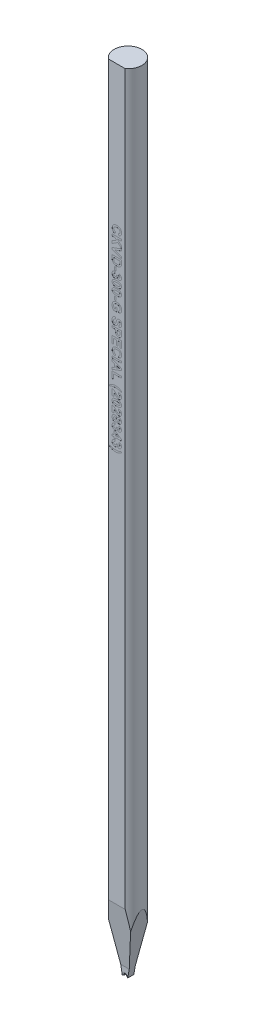
SolidWorks part; units mm, degrees
ref_plane "Ebene vorne" through (0, 0, 0) normal (0, 0, 1) x (1, 0, 0)
ref_plane "Ebene oben" through (0, 0, 0) normal (0, 1, 0) x (1, 0, 0)
ref_plane "Ebene rechts" through (0, 0, 0) normal (1, 0, 0) x (0, 0, -1)
sketch "sketch_TL_cutting" plane through (0, 0, 0) normal (0, 1, 0) x (1, 0, 0)
  circle A0 centre (0, 0) radius 1.4986
extrude "TL_cutting" add sketch "sketch_TL_cutting" along normal blind 85.4964
sketch "sketch_TDF_grinding" plane through (0, 0, 0) normal (0, 1, 0) x (1, 0, 0)
  line L0 (0, 0) -> (0, -1.2014) construction
  line L1 (-1.5086, -4.2186) -> (1.5086, -4.2186)
  line L2 (-1.5086, -4.2186) -> (-1.5086, -1.2014)
  line L3 (-1.5086, -1.2014) -> (1.5086, -1.2014)
  line L4 (1.5086, -4.2186) -> (1.5086, -1.2014)
  circle A1 centre (0, 0) radius 1.4986 construction
  point P9 (0, -4.2186)
  dimension "TD_2Offset_X" = 3.0172
  dimension "TD_2Offset_Z" = 3.0172
extrude "TDF_grinding" cut sketch "sketch_TDF_grinding" along normal through all
sketch "sketch_engraving" plane through (0, 0, 1.2014) normal (0, 0, 1) x (1, 0, 0)
  line L0 (0.8958, 85.4964) -> (-0.8958, 85.4964) construction
  line L6 (-0.8958, 0) -> (0.8958, 0) construction
  line L7 (0, 0) -> (0, 70.4964) construction
  line L8 (-0.5, 70.4964) -> (-0.5, 0) construction
  text T0 "CKVD-300-G SPECIAL (2028343)" font "Arial" height 1
  dimension "D2" = 0.5
  dimension "EngravingStart" = 15
extrude "engraving" cut sketch "sketch_engraving" against normal blind 0.005
sketch "sketch_VW_VR_grinding" plane through (0, 0, 0) normal (0, 0, 1) x (1, 0, 0)
  line L0 (-1.4936, -0.01) -> (-1.4936, 0.8842)
  line L1 (1.4936, -0.01) -> (1.4936, 0.8842)
  line L2 (-1.4936, 0) -> (1.4936, 0) construction
  line L3 (-1.5086, 0.8892) -> (-1.4986, 0.8892)
  line L4 (1.4986, 0.8892) -> (1.5086, 0.8892)
  line L5 (-1.5086, 0.8892) -> (-1.5086, -0.01)
  line L6 (-1.5086, -0.01) -> (-1.4936, -0.01)
  line L7 (1.4936, -0.01) -> (1.5086, -0.01)
  line L8 (1.5086, -0.01) -> (1.5086, 0.8892)
  line L9 (-1.4986, 0.8892) -> (-1.4986, 0.8842) construction
  line L10 (-1.4936, 0.8842) -> (-1.4986, 0.8842) construction
  line L11 (1.4936, 0.8842) -> (1.4986, 0.8842) construction
  line L12 (1.4986, 0.8892) -> (1.4986, 0.8842) construction
  arc A0 (-1.4986, 0.8892) -> (-1.4936, 0.8842) centre (-1.4986, 0.8842) cw
  arc A2 (1.4936, 0.8842) -> (1.4986, 0.8892) centre (1.4986, 0.8842) cw
  dimension "D2" = 0.005
  dimension "D1" = 0.01
  dimension "D4" = 3.0172
extrude "VW_VR_grinding" cut sketch "sketch_VW_VR_grinding" against normal blind 1.5086 and the other way blind 1.5086
sketch "sketch_ISA_grinding" plane through (0, 0, 0) normal (0, 0, 1) x (1, 0, 0)
  line L0 (-0.2997, 0) -> (-1.5086, 6.8559)
  line L4 (1.5086, 6.8559) -> (0.2997, 0)
  line L5 (0.2997, 0) -> (-0.2997, 0)
  line L6 (0, 0) -> (0, 30.49) construction
  line L7 (-1.5086, 6.8559) -> (-1.5086, -0.01)
  line L12 (-1.5086, -0.01) -> (1.5086, -0.01)
  line L13 (1.5086, -0.01) -> (1.5086, 6.8559)
  dimension "ISA" = 20
  dimension "TD_2Offset" = 3.0172
  dimension "Offset" = 0.01
extrude "ISA_grinding" cut sketch "sketch_ISA_grinding" against normal blind 1.5086 and the other way blind 1.5086
sketch "sketch_pre_FRX_BRX" plane through (0, 0, 0) normal (1, 0, 0) x (0, 0, -1)
  line L0 (1.4986, -0.01) -> (1.4986, 3.9152) construction
  line L1 (-1.2014, -0.01) -> (-1.2014, 0.8892) construction
  line L2 (-0.3251, -0.01) -> (-0.3251, 0.8892)
  line L3 (-0.3251, 0.8892) -> (-1.5086, 0.8892)
  line L4 (-1.5086, 0.8892) -> (-1.5086, -0.01)
  line L5 (-1.5086, -0.01) -> (-0.3251, -0.01)
  line L6 (0.3251, -0.01) -> (0.3251, 0.8892)
  line L7 (0.3251, 0.8892) -> (1.5086, 0.8892)
  line L8 (1.5086, 0.8892) -> (1.5086, -0.01)
  line L9 (1.5086, -0.01) -> (0.3251, -0.01)
  dimension "D3" = 0.01
  dimension "D4" = 0.8992
  dimension "D5" = 3.0172
  dimension "D6" = 0.6502
  dimension "D2" = 0.01
  dimension "D7" = 1.8237
extrude "pre_FRX_BRX" cut sketch "sketch_pre_FRX_BRX" against normal blind 1.5086 and the other way blind 1.5086
sketch "sketch_contour_V-Groove" plane through (0, 0, 0) normal (1, 0, 0) x (0, 0, -1)
  line L0 (-1.2014, 0.1905) -> (0, 0.1905)
  line L1 (0, 0.1905) -> (1.4986, 0.1905)
  line L2 (1.4986, -0.8411) -> (1.4986, 1.3178) construction
  line L3 (-1.2014, -0.9209) -> (-1.2014, 1.9363) construction
  line L4 (-1.2014, 0) -> (1.4986, 0) construction
  line L5 (0.3251, 0) -> (0.3251, 0.1905) construction
  line L6 (-0.3251, 0) -> (-0.3251, 0.1905) construction
  dimension "D1" = 0
ref_plane "front" through (0, 0, 1.2014) normal (0, 0, 1) x (1, 0, 0)
ref_plane "back" through (0, 0, -1.4986) normal (0, 0, 1) x (1, 0, 0)
sketch "sketch_section_V-Groove" plane through (0, 0, 1.2014) normal (0, 0, 1) x (1, 0, 0)
  line L0 (-1.499, -1.905) -> (-0.0499, 0.1645)
  line L2 (0.0499, 0.1645) -> (1.499, -1.905)
  line L3 (-1.499, -1.905) -> (1.499, -1.905)
  line L4 (0, -1.905) -> (0, 0.1905) construction
  line L5 (-0.1651, 0) -> (0.1651, 0) construction
  arc A0 (0.0499, 0.1645) -> (-0.0499, 0.1645) centre (0, 0.1296) ccw
  dimension "GA" = 70
sweep "V-Groove_EDM" cut profiles "sketch_section_V-Groove" path "sketch_contour_V-Groove"
fillet "FR_EDM" radius 0.1499 3 edges at (0.1075, 0.0823, 0.3251) (0, 0.1905, 0.3251) (-0.1075, 0.0823, 0.3251)
fillet "BR_EDM" radius 0.1499 3 edges at (0.1075, 0.0823, -0.3251) (0, 0.1905, -0.3251) (-0.1075, 0.0823, -0.3251)
sketch "sketch_FA_BA_grinding" plane through (0, 0, 0) normal (1, 0, 0) x (0, 0, -1)
  line L2 (2.4986, 16.3643) -> (2.4986, -0.1)
  line L3 (2.4986, -0.1) -> (0.3251, -0.1)
  line L5 (0.3251, -0.1) -> (0.3251, 0.8992)
  line L6 (0.3251, 0.8992) -> (2.4986, 16.3643)
  line L7 (1.4986, -0.1) -> (1.4986, 9.2489) construction
  line L8 (-1.2014, 7.1344) -> (-1.2014, -0.1) construction
  line L9 (-3.2728, 21.8732) -> (-0.3251, 0.8992)
  line L10 (-0.3251, 0.8992) -> (-0.3251, -0.1)
  line L11 (-0.3251, -0.1) -> (-3.2728, -0.1)
  line L12 (-3.2728, -0.1) -> (-3.2728, 21.8732)
  line L13 (-0.3251, 0.8992) -> (0.3251, 0.8992) construction
  dimension "D4" = 1
  dimension "D1" = 0.1
  dimension "FA" = 8
  dimension "BA" = 8
extrude "FA_BA_grinding" cut sketch "sketch_FA_BA_grinding" against normal blind 1.5086 and the other way blind 1.5086
sketch "sketch_groove_dimensions" plane through (0, 0, 0) normal (1, 0, 0) x (0, 0, -1)
  line L0 (-0.1753, 0.1905) -> (0.1753, 0.1905)
  line L1 (-0.3251, 0) -> (-0.3251, 0.3404) construction
  line L2 (1.4986, 0) -> (1.4986, 0.4166) construction
  line L3 (0.3251, 0) -> (0.3251, 0.3404) construction
  line L4 (-1.2014, 0) -> (-1.2014, 0.3999) construction
  arc A0 (0.1753, 0.1905) -> (0.3251, 0.3404) centre (0.1753, 0.3404) ccw
  arc A1 (-0.1753, 0.1905) -> (-0.3251, 0.3404) centre (-0.1753, 0.3404) cw
equation "\"_Offset\"=0.01mm"
equation "\"TL\"=85.4964mm"
equation "\"TD\"=2.9972mm"
equation "\"TDF\"=2.70002mm"
equation "\"BA\"=8deg"
equation "\"ISA\"=20deg"
equation "\"FA\"=8deg"
equation "\"GR\"=0.06096mm"
equation "\"GA\"=70deg"
equation "\"GD\"=0.1905mm"
equation "\"FL\"=0.65024mm"
equation "\"F\"=0.35052mm"
equation "\"FX\"=0.8763mm"
equation "\"B\"=0.3302mm"
equation "\"VW\"=0mm"
equation "\"cleaned_VR\"= IIF ( \"VR\" > 0 , \"VR\" , \"E\" - \"_Offset\" )"
equation "\"cleaned_VW\"= IIF ( \"VW\" > 0 , \"VW\" , \"TD\" - \"_Offset\" )"
equation "\"back_edge\"= \"TD\" / 2 - \"X\""
equation "\"side_edge_Offset\"= \"TD\" / 2 + \"_Offset\""
equation "\"TD@sketch_TL_cutting\"=\"TD\""
equation "\"TL@TL_cutting\"=\"TL\""
equation "\"TDF@sketch_TDF_grinding\"=\"TDF\""
equation "\"TD_2Offset_X@sketch_TDF_grinding\"=\"TD\"+2*\"_Offset\""
equation "\"TD_2Offset_Z@sketch_TDF_grinding\"=\"TD\"+2*\"_Offset\""
equation "\"TL_Offset\"= \"TL\" + \"_Offset\""
equation "\"ISA@sketch_ISA_grinding\"=\"ISA\""
equation "\"W@sketch_ISA_grinding\"=\"W\""
equation "\"TD_2Offset@sketch_ISA_grinding\"=\"TD\"+2*\"_Offset\""
equation "\"Offset@sketch_ISA_grinding\"=\"_Offset\""
equation "\"05TD_Offset_posZ@ISA_grinding\"=\"side_edge_Offset\""
equation "\"05TD_Offset_negZ@ISA_grinding\"=\"side_edge_Offset\""
equation "\"E\"=0.89916mm"
equation "\"cleaned_X\"= IIF ( \"X\" > 0 , \"X\" , \"TD\" / 2 - \"FL\" / 2 )"
equation "\"FR\"=0.14986mm"
equation "\"BR\"=0.14986mm"
equation "\"D1\"= \"side_edge_Offset\""
equation "\"D2\"= \"side_edge_Offset\""
equation "\"TDF@sketch_FA_BA_grinding\" = \"TDF\""
equation "\"FL@sketch_FA_BA_grinding\"=\"FL\""
equation "\"E@sketch_FA_BA_grinding\" = \"E\""
equation "\"D1@FA_BA_grinding\"=\"side_edge_Offset\""
equation "\"D2@FA_BA_grinding\"=\"side_angle_Offset\""
equation "\"10GD@sketch_section_V-Groove\" = 10 * \"GD\""
equation "\"GA@sketch_section_V-Groove\" = \"GA\""
equation "\"GD@sketch_section_V-Groove\" = \"GD\""
equation "\"B@sketch_section_V-Groove\" = \"B\""
equation "\"GD@sketch_contour_V-Groove\" = \"GD\""
equation "\"cleaned_FRX\"= IIF ( \"FRX\" > 0 , \"FRX\" , \"FR\" )"
equation "\"cleaned_BRX\"= IIF ( \"BRX\" > 0 , \"BRX\" , \"BR\" )"
equation "\"FL_groove_angle\"=0deg"
equation "\"D3@sketch_pre_FRX_BRX\" = \"_Offset\""
equation "\"D4@sketch_pre_FRX_BRX\" = \"E\""
equation "\"D5@sketch_pre_FRX_BRX\" = 2 * \"side_edge_Offset\""
equation "\"D6@sketch_pre_FRX_BRX\" = \"FL\" + ( \"FR\" - \"cleaned_FRX\" ) + ( \"BR\" - \"cleaned_BRX\" )"
equation "\"TD/2@sketch_pre_FRX_BRX\" = \"TD\" / 2"
equation "\"TDF@sketch_pre_FRX_BRX\" = \"TDF\""
equation "\"D2@sketch_pre_FRX_BRX\" = \"_Offset\""
equation "\"D1@pre_FRX_BRX\" = \"side_edge_Offset\""
equation "\"D2@pre_FRX_BRX\" = \"side_edge_Offset\""
equation "\"D1@BR_EDM\"=\"BR\""
equation "\"TD/2@sketch_FA_BA_grinding\" = \"TD\" / 2"
equation "\"TD/2@sketch_contour_V-Groove\" = \"TD\" / 2"
equation "\"TDF@sketch_contour_V-Groove\" = \"TDF\""
equation "\"D1@sketch_contour_V-Groove\"=\"FL_groove_angle\""
equation "\"FL@sketch_contour_V-Groove\"=\"FL\""
equation "\"FL/2@sketch_contour_V-Groove\" = \"FL\" / 2"
equation "\"D1@FR_EDM\"=\"FR\""
equation "\"D1@sketch_VW_VR_grinding\" = \"_Offset\""
equation "\"D4@sketch_VW_VR_grinding\" = 2 * \"side_edge_Offset\""
equation "\"VR@sketch_VW_VR_grinding\" = \"cleaned_VR\""
equation "\"VW@sketch_VW_VR_grinding\"=\"cleaned_VW\""
equation "\"D1@VW_VR_grinding\" = \"side_edge_Offset\""
equation "\"D2@VW_VR_grinding\" = \"side_edge_Offset\""
equation "\"X\"=0mm"
equation "\"VR\"=0mm"
equation "\"W\"=0.59944mm"
equation "\"VW_radius\"= \"cleaned_VW\" / 10"
equation "\"VW_radius_cleaned\"= IIF ( \"VW\" > 0 , \"VW_radius\" , \"_Offset\" / 2 )"
equation "\"D2@sketch_VW_VR_grinding\"=\"VW_radius_cleaned\""
equation "\"FRX\"=0mm"
equation "\"BRX\"=0mm"
equation "\"FA@sketch_FA_BA_grinding\" = \"FA\""
equation "\"D4@sketch_FA_BA_grinding\"=\"_Offset\"*100"
equation "\"BA@sketch_FA_BA_grinding\" = \"BA\""
equation "\"D1@sketch_groove_dimensions\" = \"TD\" / 2"
equation "\"FL@sketch_groove_dimensions\" = \"FL\""
equation "\"FR@sketch_groove_dimensions\" = \"FR\""
equation "\"BR@sketch_groove_dimensions\" = \"BR\""
equation "\"FRX@sketch_groove_dimensions\" = \"cleaned_FRX\""
equation "\"BRX@sketch_groove_dimensions\" = \"cleaned_BRX\""
equation "\"GD@sketch_groove_dimensions\" = \"GD\""
equation "\"cleaned_FX\"= IIF ( \"FX\" > 0 , \"FX\" , \"TDF\" - ( \"TD\" + \"FL\" ) / 2 )"
equation "\"D7@sketch_pre_FRX_BRX\"=\"TDF\"-\"cleaned_FX\"-(\"FR\"-\"cleaned_FRX\")"
equation "\"FX@sketch_contour_V-Groove\" = \"cleaned_FX\""
equation "\"FX@sketch_FA_BA_grinding\" = \"cleaned_FX\""
equation "\"TDF@sketch_groove_dimensions\" = \"TDF\""
equation "\"FX@sketch_groove_dimensions\" = \"cleaned_FX\""
equation "\"EngravingStart\"=15mm"
equation "\"EngravingStart@sketch_engraving\" = \"EngravingStart\""
